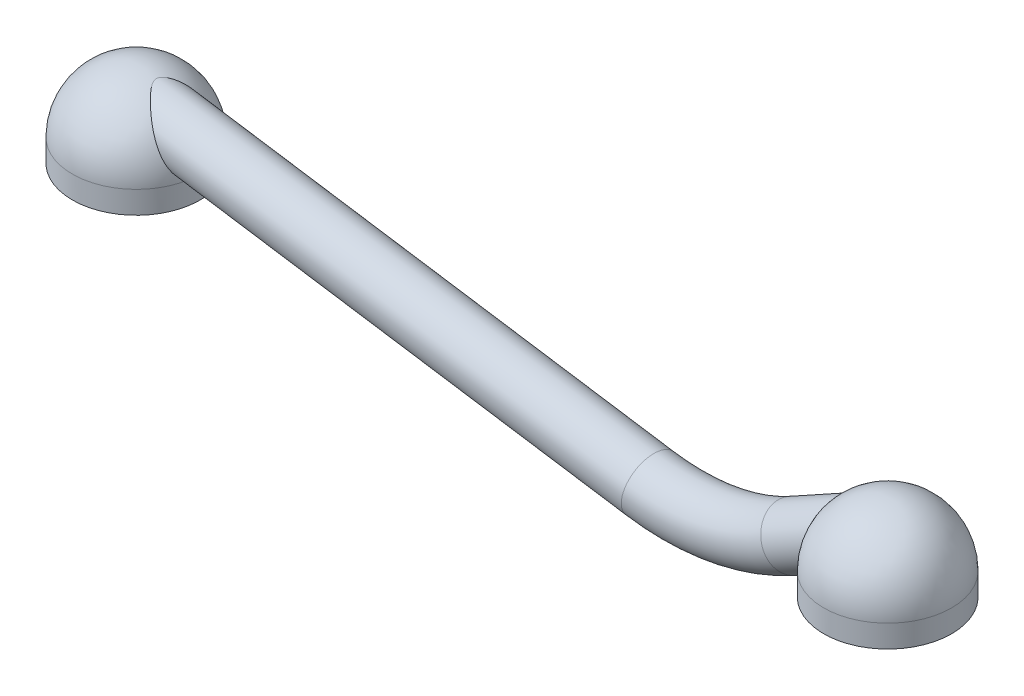
SolidWorks part; units mm, degrees
note: The reader was unsure of these and kept them because the rebuilt part matched: shared geometry of "Sketch2<3>", "Sketch3<3>".
ref_plane "Front Plane" through (0, 0, 0) normal (0, 0, 1) x (1, 0, 0)
ref_plane "Top Plane" through (0, 0, 0) normal (0, 1, 0) x (1, 0, 0)
ref_plane "Right Plane" through (0, 0, 0) normal (1, 0, 0) x (0, 0, -1)
sketch "Sketch1" plane through (0, 0, 0) normal (0, 1, 0) x (1, 0, 0)
  line L0 (0, 0) -> (39.2, 0) construction
  circle A0 centre (2.85, 0) radius 2.85
  circle A1 centre (36.35, 0) radius 2.85
  circle A2 centre (36.35, 0) radius 1.9
  circle A3 centre (2.85, 0) radius 1.9
  dimension "D2" = 5.7
  dimension "D3" = 3.8
  dimension "D1" = 39.2
extrude "Boss-Extrude1" add sketch "Sketch1" along normal blind 1
sketch "Sketch2" plane through (0, 0, 0) normal (0, 0, 1) x (1, 0, 0)
  line L0 (5.7, 1) -> (0, 1) construction
  line L1 (2.85, 3.85) -> (2.85, 2.9)
  line L2 (0.95, 1) -> (0, 1)
  line L3 (2.85, 2.9) -> (2.85, 0)
  line L4 (0, 0) -> (5.7, 0) construction
  line L5 (2.85, 0) -> (0.95, 0)
  line L6 (0.95, 0) -> (0.95, 1)
  arc A0 (0, 1) -> (2.85, 3.85) centre (2.85, 1) cw
  arc A1 (0.95, 1) -> (2.85, 2.9) centre (2.85, 1) cw
  dimension "D1" = 1.9
revolve "Revolve1" add sketch "Sketch2" angle 360 about L1
sketch "Sketch3" plane through (0, 0, 0) normal (0, 0, 1) x (1, 0, 0)
  line L0 (38.25, 1) -> (34.45, 1) construction
  line L1 (36.35, 3.85) -> (36.35, 2.9)
  line L2 (34.45, 1) -> (33.5, 1)
  line L3 (36.35, 2.9) -> (36.35, 0)
  line L4 (33.5, 0) -> (39.2, 0) construction
  line L5 (36.35, 0) -> (34.45, 0)
  line L6 (34.45, 0) -> (34.45, 1)
  arc A0 (33.5, 1) -> (36.35, 3.85) centre (36.35, 1) cw
  arc A1 (34.45, 1) -> (36.35, 2.9) centre (36.35, 1) cw
revolve "Revolve2" add sketch "Sketch3" angle 360 about L1
sketch "Sketch4" plane through (0, 0, 0) normal (0, 0, 1) x (1, 0, 0)
  line L0 (2.8578, 2.5771) -> (25.7353, -0.9101)
  line L1 (32.0789, 0.2233) -> (36.3383, 2.5771)
  line L2 (33.5, 1) -> (33.5, 0) construction
  arc A0 (25.7353, -0.9101) -> (32.0789, 0.2233) centre (27.2422, 8.9758) ccw
  point P2 (33.5, 1.0086)
  point P4 (0, 0)
  point P7 (2.929, 2.357)
  point P8 (36.4095, 2.357)
  point P9 (29.1, -2.3381)
  point P10 (34.593, 1.8647)
  point P11 (29.1, -3.5491)
  point P12 (29.1, -1.4833)
  point P13 (36.4095, 3.1826)
  point P14 (36.3383, 2.5771)
  point P15 (2.8578, 2.5771)
  point P18 (29.1, -1.4229)
  dimension "D3" = 10
  dimension "D1" = 4
  dimension "D2" = 4.4
ref_plane "Plane1" through (2.8578, 2.5771, 0) normal (0.9886, -0.1507, 0) x (0, 0, -1)
sketch "Sketch6" plane through (2.8578, 2.5771, 0) normal (0.9886, -0.1507, 0) x (0, 0, -1)
  circle A0 centre (0, 0) radius 1.25
  dimension "D1" = 2.5
sweep "Sweep2" add profiles "Sketch6" path "Sketch4"
revolve "Cut-Revolve2" cut sketch "Sketch2<3>" angle 360 about L3
sketch "Sketch2<3>" plane through (0, 0, 0) normal (0, 0, 1) x (1, 0, 0) same geometry as "Sketch2"
revolve "Cut-Revolve3" cut sketch "Sketch3<3>" angle 360 about L3
sketch "Sketch3<3>" plane through (0, 0, 0) normal (0, 0, 1) x (1, 0, 0) same geometry as "Sketch3"
